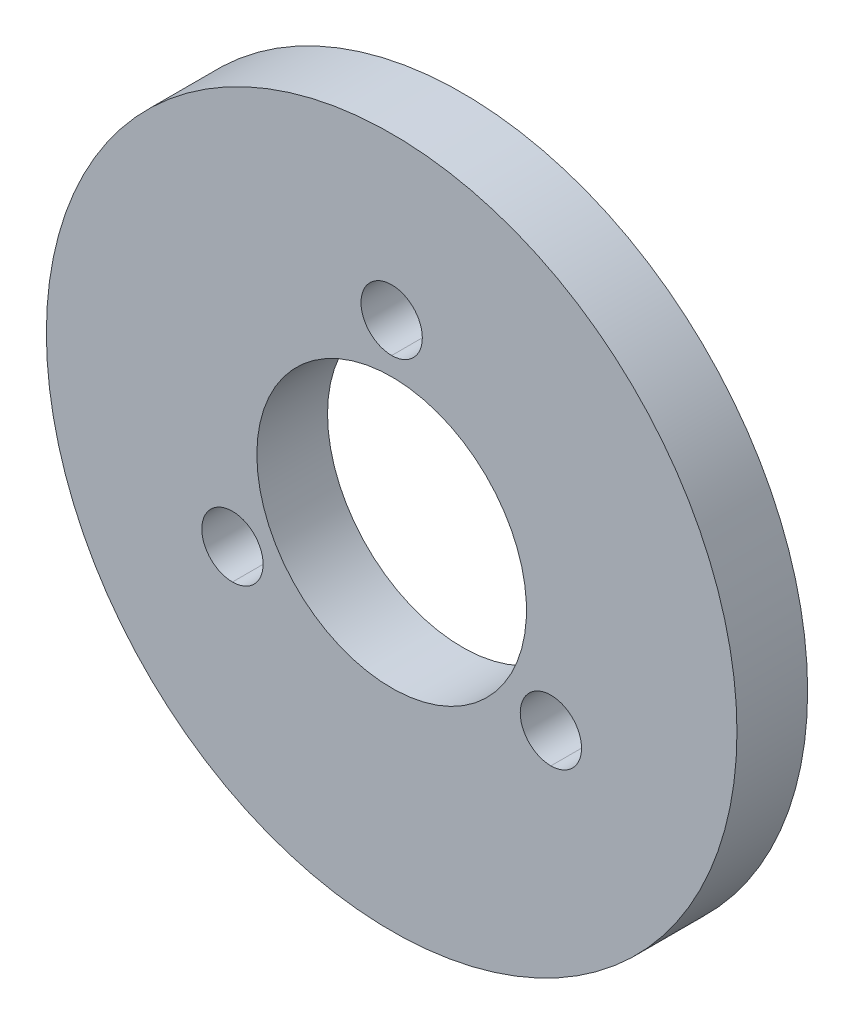
SolidWorks part; units mm, degrees
ref_plane "Front Plane" through (0, 0, 0) normal (0, 0, 1) x (1, 0, 0)
ref_plane "Top Plane" through (0, 0, 0) normal (0, 1, 0) x (1, 0, 0)
ref_plane "Right Plane" through (0, 0, 0) normal (1, 0, 0) x (0, 0, -1)
sketch "Sketch1" plane through (0, 0, 0) normal (0, 0, 1) x (1, 0, 0)
  line L0 (-10.7121, 2.5) -> (-8.6458, 2.5) construction
  line L1 (-10.7121, -2.5) -> (-8.6458, -2.5) construction
  line L2 (-9.679, 2.5) -> (-9.679, -2.5) construction
  line L3 (-3.191, 10.527) -> (-2.1578, 8.7375) construction
  line L4 (-7.5211, 8.027) -> (-6.488, 6.2375) construction
  line L5 (7.5211, 8.027) -> (6.488, 6.2375) construction
  line L6 (3.191, 10.527) -> (2.1578, 8.7375) construction
  line L7 (10.7121, -2.5) -> (8.6458, -2.5) construction
  line L8 (10.7121, 2.5) -> (8.6458, 2.5) construction
  line L9 (3.191, -10.527) -> (2.1578, -8.7375) construction
  line L10 (7.5211, -8.027) -> (6.488, -6.2375) construction
  line L11 (-7.5211, -8.027) -> (-6.488, -6.2375) construction
  line L12 (-3.191, -10.527) -> (-2.1578, -8.7375) construction
  circle A0 centre (0, 0) radius 28.1739
  arc A1 (-8.6458, -2.5) -> (-6.488, -6.2375) centre (0, 0) ccw construction
  arc A2 (-10.7121, 2.5) -> (-10.7121, -2.5) centre (0, 0) ccw construction
  arc A3 (-6.488, 6.2375) -> (-8.6458, 2.5) centre (0, 0) ccw construction
  arc A4 (2.1578, 8.7375) -> (-2.1578, 8.7375) centre (0, 0) ccw construction
  arc A5 (8.6458, 2.5) -> (6.488, 6.2375) centre (0, 0) ccw construction
  arc A6 (6.488, -6.2375) -> (8.6458, -2.5) centre (0, 0) ccw construction
  arc A7 (-2.1578, -8.7375) -> (2.1578, -8.7375) centre (0, 0) ccw construction
  arc A8 (-7.5211, -8.027) -> (-3.191, -10.527) centre (0, 0) ccw construction
  arc A9 (3.191, -10.527) -> (7.5211, -8.027) centre (0, 0) ccw construction
  arc A10 (10.7121, -2.5) -> (10.7121, 2.5) centre (0, 0) ccw construction
  arc A11 (7.5211, 8.027) -> (3.191, 10.527) centre (0, 0) ccw construction
  arc A12 (-3.191, 10.527) -> (-7.5211, 8.027) centre (0, 0) ccw construction
  circle A13 centre (0, 15) radius 2.5
  circle A14 centre (12.9904, -7.5) radius 2.5
  circle A15 centre (-12.9904, -7.5) radius 2.5
  circle A16 centre (0, 0) radius 11
  point P11 (-9.679, 0)
  point P34 (0, 0)
  point P39 (0, 0)
  dimension "D1" = 56.3478
  dimension "D2" = 22
  dimension "D3" = 18
  dimension "D7" = 5
  dimension "D4" = 5
  dimension "D5" = 6
  dimension "D6" = 15
  dimension "D8" = 3
extrude "Boss-Extrude1" add sketch "Sketch1" along normal blind 5.7658
ref_plane "Motor Sprocket Middle Plane" through (0, 0, 2.8829) normal (0, 0, 1) x (1, 0, 0)
sketch "Sketch3" plane through (0, 0, 5.7658) normal (0, 0, 1) x (1, 0, 0)
  circle A0 centre (0, 15) radius 2.5 construction
  circle A1 centre (-12.9904, -7.5) radius 2.5 construction
  circle A2 centre (12.9904, -7.5) radius 2.5 construction
  point P0 (0, 17.5)
  point P1 (0, 12.5)
  point P4 (-12.9904, -5)
  point P5 (-12.9904, -10)
  point P8 (12.9904, -5)
  point P9 (12.9904, -10)
sketch "Sketch4" plane through (0, 0, 0) normal (0, 0, -1) x (-1, 0, 0)
  point P0 (12.9904, -5)
  point P2 (12.9904, -10)
  point P4 (-12.9904, -10)
  point P6 (-12.9904, -5)
  point P8 (0, 12.5)
  point P10 (0, 17.5)
ref_plane "Plane1" through (12.9904, 0, 0) normal (1, 0, 0) x (0, 0, -1)
ref_plane "Plane2" through (0, 0, 0) normal (1, 0, 0) x (0, 0, -1)
ref_plane "Plane3" through (-12.9904, 0, 0) normal (1, 0, 0) x (0, 0, -1)
ref_axis "Axis2" through (0, 0, 5.7658) along (0, 0, -1)
split line "Split Line1"
split line "Split Line2"
split line "Split Line3"
